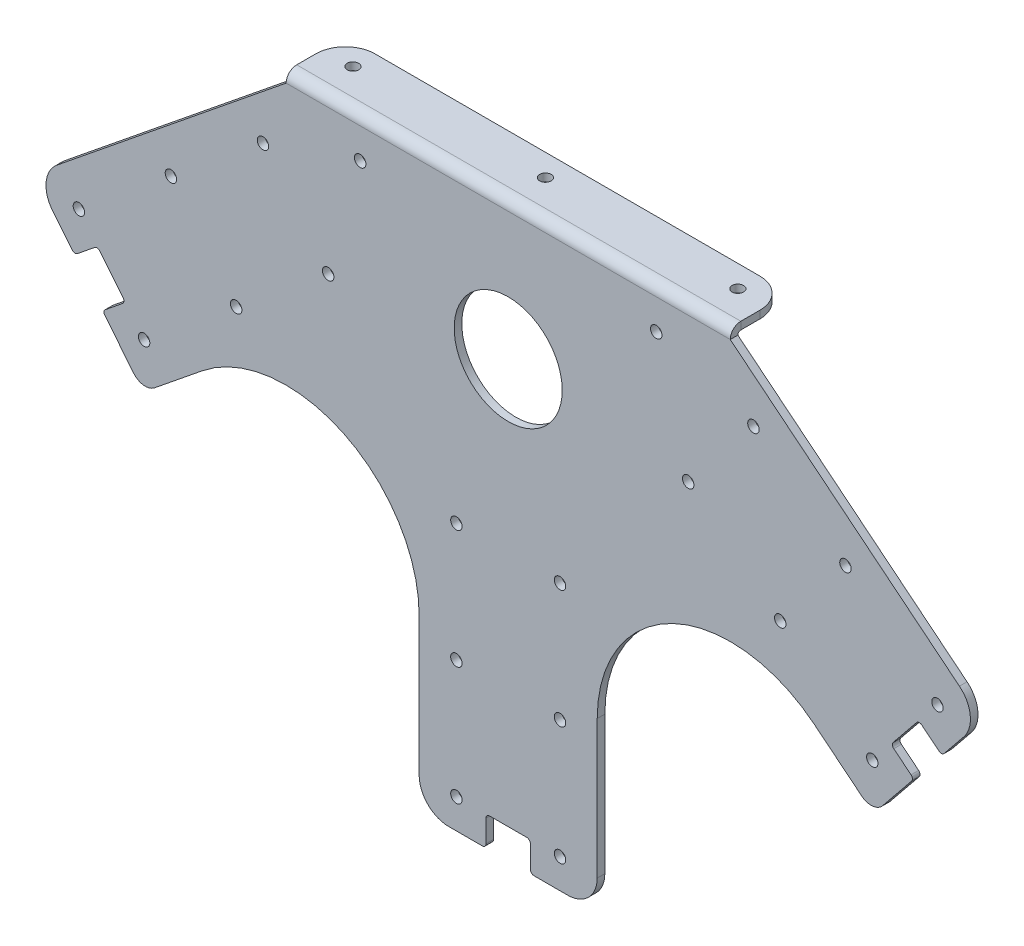
SolidWorks part; units mm, degrees
note: The reader was unsure of these and kept them because the rebuilt part matched: flange length of "Edge-Flange1".
material "5052-H32"
ref_plane "Front Plane" through (0, 0, 0) normal (0, 0, 1) x (1, 0, 0)
ref_plane "Top Plane" through (0, 0, 0) normal (0, 1, 0) x (1, 0, 0)
ref_plane "Right Plane" through (0, 0, 0) normal (1, 0, 0) x (0, 0, -1)
sketch "Sketch1" plane through (0, 0, 0) normal (0, 0, 1) x (1, 0, 0)
  line L0 (0, 0) -> (0, -50000) construction
  line L1 (95.25, 54.9275) -> (-95.25, 54.9275)
  line L2 (-95.25, 54.9275) -> (-203.4372, -32.6808) construction
  line L4 (-156.6259, -90.488) -> (0, 36.3452) construction
  line L5 (-38.1889, -186.3725) -> (-38.1889, 5.4205) construction
  line L8 (38.1889, -186.3725) -> (38.1889, 5.4205) construction
  line L9 (156.6259, -90.488) -> (0, 36.3452) construction
  line L10 (95.25, 54.9275) -> (203.4372, -32.6808) construction
  line L11 (-203.4372, -32.6808) -> (-156.6259, -90.488)
  line L12 (-156.6259, -90.488) -> (-38.1889, -186.3725)
  line L13 (156.6259, -90.488) -> (203.4372, -32.6808)
  line L14 (38.1889, -186.3725) -> (156.6259, -90.488)
  line L15 (-95.25, 54.9275) -> (-203.4372, -32.6808)
  line L16 (203.4372, -32.6808) -> (95.25, 54.9275)
  line L17 (38.1889, -186.3725) -> (-38.1889, -186.3725)
  circle A0 centre (0, 0) radius 23.1775
  point P7 (0, 23.1775)
  point P15 (0, -186.3725)
  point P20 (0, 54.9275)
  dimension "D1" = 46.355
  dimension "D2" = 39
  dimension "D3" = 95.25
  dimension "D4" = 31.75
  dimension "D5" = 241.3
  dimension "D6" = 74.3839
  dimension "D7" = 38.1889
  dimension "D8" = 152.4
base flange "Base-Flange1" sketch "Sketch1" thickness 3.2639 reverse thickness direction no parameters "D1"=1.27
edge flange "Edge-Flange1" sketch "Sketch8" flange angle 90 flange length 25.4 flange position bend outside bend radius 1.27 thickness 3.2639 relief rectangular parameters "D6"=10
sketch "Sketch8" plane through (0, 54.9275, -3.2639) normal (0, -1, 0) x (-1, 0, 0)
  line L2 (-95.25, 0) -> (-95.25, 22.1361)
  line L3 (-95.25, 22.1361) -> (95.25, 22.1361)
  line L4 (95.25, 22.1361) -> (95.25, 0)
  line L5 (95.25, 0) -> (-95.25, 0) construction
  line L6 (95.25, 0) -> (-95.25, 0)
bend "EdgeBend1" bend radius 1.27 bend angle 90 parameters "D5"=1
edge flange "Edge-Flange2" [suppressed] sketch "Sketch11" flange angle 90 flange position material inside bend radius 1.27 thickness 3.2639
sketch "Sketch11" plane through (0, 56.1975, -25.4) normal (0, 0, 1) x (-1, 0, 0)
  line L2 (-95.25, 0) -> (-95.25, 9.4361)
  line L3 (-95.25, 9.4361) -> (95.25, 9.4361)
  line L4 (95.25, 9.4361) -> (95.25, 0)
  line L5 (95.25, 0) -> (-95.25, 0) construction
  line L6 (95.25, 0) -> (-95.25, 0)
bend "EdgeBend2" bend radius 1.27 bend angle 90 parameters "D5"=2, "D6"=10, "D7"=12.7
sketch "Sketch12" [suppressed] plane through (0, 0, -25.4) normal (0, 0, -1) x (-1, 0, 0)
  line L4 (199.0941, -29.1638) -> (95.25, 54.9275)
  line L5 (95.25, 54.9275) -> (-95.25, 54.9275)
  line L6 (199.0941, -29.1638) -> (95.25, 54.9275)
  line L7 (-95.25, 54.9275) -> (-199.0941, -29.1638)
  line L12 (95.25, 46.7614) -> (95.25, 54.9275)
  line L13 (95.25, 54.9275) -> (-95.25, 54.9275)
  line L14 (-95.25, 54.9275) -> (-95.25, 46.7614)
  line L15 (-95.25, 46.7614) -> (95.25, 46.7614)
  line L16 (95.25, 46.7614) -> (95.25, 54.9275)
  line L18 (-95.25, 54.9275) -> (-95.25, 46.7614)
  line L19 (-95.25, 46.7614) -> (95.25, 46.7614)
  line L24 (-95.25, 54.9275) -> (-199.0941, -29.1638)
  line L25 (-199.0941, -29.1638) -> (-143.1475, -98.2521)
  line L26 (-199.0941, -29.1638) -> (-143.1475, -98.2521)
  line L27 (-143.1475, -98.2521) -> (-44.45, -186.3725)
  line L28 (-143.1475, -98.2521) -> (-44.45, -186.3725)
  line L29 (-44.45, -186.3725) -> (44.45, -186.3725)
  line L30 (-44.45, -186.3725) -> (44.45, -186.3725)
  line L31 (44.45, -186.3725) -> (143.1475, -98.2521)
  line L32 (44.45, -186.3725) -> (143.1475, -98.2521)
  line L33 (143.1475, -98.2521) -> (199.0941, -29.1638)
  line L34 (143.1475, -98.2521) -> (199.0941, -29.1638)
  circle A0 centre (0, 0) radius 23.1775 construction
  circle A1 centre (0, 0) radius 23.1775
  dimension "D1" = 0
  dimension "D2" = 0
extrude "Boss-Extrude1" [suppressed] add sketch "Sketch12" against normal up to surface (3.2639 mm away)
sketch "Sketch13" plane through (0, 0, 0) normal (0, 0, 1) x (1, 0, 0)
  line L0 (-156.6259, -90.488) -> (-38.1889, 5.4205)
  line L1 (-38.1889, 5.4205) -> (-38.1889, -186.3725)
  line L2 (38.1889, -186.3725) -> (38.1889, 5.4205)
  line L3 (38.1889, 5.4205) -> (156.6259, -90.488)
  line L6 (-38.1889, -186.3725) -> (-156.6259, -90.488)
  line L7 (38.1889, -186.3725) -> (156.6259, -90.488)
extrude "Cut-Extrude1" cut sketch "Sketch13" along normal through all and the other way through all normal cut yes
fillet "Fillet1" radius 57.15 2 edges at (38.1889, 5.4205, -1.6319) (-38.1889, 5.4205, -1.6319)
sketch "Sketch14" plane through (0, 0, 0) normal (0, 0, 1) x (1, 0, 0)
  line L0 (-154.0885, 7.281) -> (-107.2772, -50.5261) construction
  line L1 (-95.25, 54.9275) -> (-203.4372, -32.6808) construction
  line L2 (-156.6259, -90.488) -> (-131.3046, -69.9831) construction
  line L3 (-203.4372, -32.6808) -> (-156.6259, -90.488) construction
  line L4 (-144.6695, -4.3505) -> (-105.1905, 27.619) construction
  line L5 (-105.1905, 27.619) -> (-77.2172, -6.9251) construction
  line L6 (-77.2172, -6.9251) -> (-116.6962, -38.8946) construction
  line L7 (-184.1485, -36.3199) -> (-156.1752, -70.8641) construction
  line L8 (0, 0) -> (0, -186.3725) construction
  line L9 (-38.1889, -186.3725) -> (38.1889, -186.3725) construction
  point P4 (-116.6962, -38.8946)
  point P9 (-144.6695, -4.3505)
  point P10 (-105.1905, 27.619)
  point P11 (-77.2172, -6.9251)
  point P14 (-184.1485, -36.3199)
  point P17 (-156.1752, -70.8641)
  point P25 (77.2172, -6.9251)
  point P26 (116.6962, -38.8946)
  point P27 (156.1752, -70.8641)
  point P28 (184.1485, -36.3199)
  point P29 (144.6695, -4.3505)
  point P30 (105.1905, 27.619)
  dimension "D1" = 114.3
  dimension "D2" = 14.9669
  dimension "D3" = 44.45
  dimension "D4" = 50.8
  dimension "D5" = 50.8
hole_wizard "#10 (0.1935) Diameter Hole2" positions "Sketch15" profile "Sketch16" hole size "#10" standard "ANSI Inch" end condition through all
sketch "Sketch15" plane through (0, 0, 0) normal (0, 0, 1) x (1, 0, 0)
  point P0 (-144.6695, -4.3505)
  point P3 (-116.6962, -38.8946)
  point P6 (-77.2172, -6.9251)
  point P8 (-105.1905, 27.619)
  point P10 (-156.1752, -70.8641)
  point P12 (-184.1485, -36.3199)
  point P14 (105.1905, 27.619)
  point P17 (77.2172, -6.9251)
  point P20 (144.6695, -4.3505)
  point P23 (116.6962, -38.8946)
  point P26 (156.1752, -70.8641)
  point P29 (184.1485, -36.3199)
sketch "Sketch16" plane through (-144.6695, -4.3505, 0) normal (1, 0, 0) x (0, -1, 0)
  line L0 (0, 0) -> (0, 25.4)
  line L1 (0, 25.4) -> (2.4574, 25.4)
  line L2 (2.4574, 25.4) -> (2.4574, 0)
  line L5 (2.4574, 0) -> (0, 0)
  line L11 (0, -6.35) -> (0, 107.95) construction
  dimension "Thru Hole Dia." = 4.9149
  dimension "Thru Hole Depth" = 25.4
mirror "Mirror1" [suppressed] about plane through (0, 0, 0) normal (1, 0, 0)
sketch "Sketch17" plane through (0, 0, 0) normal (0, 0, 1) x (1, 0, 0)
  line L0 (-38.1889, -186.3725) -> (38.1889, -186.3725) construction
  line L1 (-22.225, -173.6725) -> (22.225, -173.6725)
  line L2 (-22.225, -173.6725) -> (-22.225, -122.8725)
  line L3 (-22.225, -122.8725) -> (22.225, -122.8725)
  line L4 (22.225, -173.6725) -> (22.225, -122.8725)
  point P6 (0, -186.3725)
  point P7 (0, -173.6725)
  point P8 (-22.225, -72.0725)
  point P9 (22.225, -72.0725)
  dimension "D1" = 44.45
  dimension "D2" = 50.8
  dimension "D3" = 12.7
  dimension "D4" = 50.8
hole_wizard "#10 (0.1935) Diameter Hole1" positions "Sketch18" profile "Sketch19" hole size "#10" standard "ANSI Inch" end condition through all
sketch "Sketch18" plane through (0, 0, 0) normal (0, 0, 1) x (1, 0, 0)
  point P0 (-22.225, -173.6725)
  point P3 (-22.225, -122.8725)
  point P6 (-22.225, -72.0725)
  point P9 (22.225, -72.0725)
  point P12 (22.225, -122.8725)
  point P15 (22.225, -173.6725)
sketch "Sketch19" plane through (-22.225, -173.6725, 0) normal (1, 0, 0) x (0, -1, 0)
  line L0 (0, 0) -> (0, 25.4)
  line L1 (0, 25.4) -> (2.4574, 25.4)
  line L2 (2.4574, 25.4) -> (2.4574, 0)
  line L5 (2.4574, 0) -> (0, 0)
  line L11 (0, -6.35) -> (0, 107.95) construction
  dimension "Thru Hole Dia." = 4.9149
  dimension "Thru Hole Depth" = 25.4
sketch "Sketch20" plane through (0, 0, 0) normal (0, 0, 1) x (1, 0, 0)
  line L0 (156.6259, -90.488) -> (203.4372, -32.6808) construction
  line L1 (-38.1889, -186.3725) -> (38.1889, -186.3725) construction
  line L2 (-203.4372, -32.6808) -> (-156.6259, -90.488) construction
  line L3 (156.6259, -90.488) -> (203.4372, -32.6808) construction
  line L4 (-38.1889, -186.3725) -> (38.1889, -186.3725) construction
  line L5 (-203.4372, -32.6808) -> (-156.6259, -90.488) construction
  line L6 (-186.0259, -54.1821) -> (-176.1561, -46.1897)
  line L7 (-176.1561, -46.1897) -> (-164.1676, -60.9943)
  line L8 (-164.1676, -60.9943) -> (-174.0373, -68.9867)
  line L9 (-9.525, -186.3725) -> (-9.525, -173.6725)
  line L10 (-9.525, -173.6725) -> (9.525, -173.6725)
  line L11 (9.525, -173.6725) -> (9.525, -186.3725)
  line L12 (174.0373, -68.9867) -> (164.1676, -60.9943)
  line L13 (164.1676, -60.9943) -> (176.1561, -46.1897)
  line L14 (176.1561, -46.1897) -> (186.0259, -54.1821)
  line L15 (-186.0259, -54.1821) -> (-174.0373, -68.9867)
  line L16 (-9.525, -186.3725) -> (9.525, -186.3725)
  line L17 (186.0259, -54.1821) -> (174.0373, -68.9867)
  point P19 (-180.0316, -61.5844)
  point P20 (-180.0316, -61.5844)
  point P21 (0, -186.3725)
  point P22 (0, -186.3725)
  point P23 (180.0316, -61.5844)
  point P24 (180.0316, -61.5844)
  dimension "D1" = 19.05
  dimension "D2" = 12.7
extrude "Cut-Extrude2" cut sketch "Sketch20" against normal through all normal cut yes
sketch "Sketch21" plane through (0, 59.4614, 0) normal (0, 1, 0) x (1, 0, 0)
  line L1 (-95.25, 3.2639) -> (-203.4372, 3.2639) construction
  line L2 (-82.55, 15.9639) -> (0, 15.9639) construction
  line L3 (0, 15.9639) -> (82.55, 15.9639) construction
  line L4 (-95.25, 4.5339) -> (-95.25, 25.4) construction
  point P0 (-82.55, 15.9639)
  point P1 (0, 15.9639)
  point P2 (82.55, 15.9639)
  dimension "D1" = 12.7
  dimension "D2" = 12.7
hole_wizard "#10 (0.1935) Diameter Hole3" positions "Sketch22" profile "Sketch23" hole size "#10" standard "ANSI Inch" end condition up to next
sketch "Sketch22" plane through (0, 59.4614, 0) normal (0, 1, 0) x (1, 0, 0)
  point P0 (-82.55, 15.9639)
  point P3 (0, 15.9639)
  point P6 (82.55, 15.9639)
sketch "Sketch23" plane through (-82.55, 59.4614, -15.9639) normal (1, 0, 0) x (0, 0, 1)
  line L0 (0, 0) -> (0, 3.2639)
  line L1 (0, 3.2639) -> (2.4574, 3.2639)
  line L2 (2.4574, 3.2639) -> (2.4574, 0)
  line L5 (2.4574, 0) -> (0, 0)
  line L11 (0, -6.35) -> (0, 107.95) construction
  dimension "Thru Hole Dia." = 4.9149
  dimension "Thru Hole Depth" = 3.2639
sketch "Sketch25" plane through (0, 0, 0) normal (0, 0, 1) x (1, 0, 0)
  line L1 (-95.25, 56.1975) -> (95.25, 56.1975) construction
  line L3 (-63.5, 41.91) -> (63.5, 41.91) construction
  point P0 (-63.5, 41.91)
  point P1 (63.5, 41.91)
  point P6 (0, 41.91)
  point P7 (-63.5, -34.29)
  point P8 (63.5, -34.29)
  dimension "D1" = 14.2875
  dimension "D2" = 127
  dimension "D3" = 76.2
hole_wizard "#10 (0.1935) Diameter Hole4" positions "Sketch26" profile "Sketch27" hole size "#10" standard "ANSI Inch" end condition up to next
sketch "Sketch26" plane through (0, 0, 0) normal (0, 0, 1) x (1, 0, 0)
  point P0 (-63.5, 41.91)
  point P3 (63.5, 41.91)
sketch "Sketch27" plane through (-63.5, 41.91, 0) normal (1, 0, 0) x (0, -1, 0)
  line L0 (0, 0) -> (0, 3.2639)
  line L1 (0, 3.2639) -> (2.4574, 3.2639)
  line L2 (2.4574, 3.2639) -> (2.4574, 0)
  line L5 (2.4574, 0) -> (0, 0)
  line L11 (0, -6.35) -> (0, 107.95) construction
  dimension "Thru Hole Dia." = 4.9149
  dimension "Thru Hole Depth" = 3.2639
fillet "Fillet2" radius 12.7 6 edges at (203.4372, -32.6808, -1.632) (38.1889, -186.3725, -1.6319) (-38.1889, -186.3725, -1.6319) (-203.4372, -32.6808, -1.632) (95.25, 57.8295, -25.4) (-95.25, 57.8295, -25.4)
fillet "Fillet3" radius 1.5875 12 edges at (164.1676, -60.9943, -1.632) (174.0373, -68.9867, -1.632) (186.0259, -54.1821, -1.632) (176.1561, -46.1897, -1.632) (9.525, -173.6725, -1.632) (9.525, -186.3725, -1.632) (-9.525, -186.3725, -1.632) (-9.525, -173.6725, -1.632) (-176.1561, -46.1897, -1.632) (-174.0373, -68.9867, -1.632) (-164.1676, -60.9943, -1.632) (-186.0259, -54.1821, -1.632)
fillet "Fillet4" radius 6.35 2 edges at (156.6259, -90.488, -1.6319) (-156.6259, -90.488, -1.6319)
sketch "Bend-Lines1" [suppressed] plane through (0, 0, 0) normal (0, 1, 0) x (1, 0, 0)
sketch "Bounding-Box1" [suppressed] plane through (0, 0, 0) normal (0, 1, 0) x (1, 0, 0)
sheet metal parameters "Sheet-Metal1" thickness 3.2639 parameters "D1"=1.27
flat pattern "Flat-Pattern1" [suppressed]
sketch "Bend-Lines2" plane through (0, 0, 0) normal (0, 1, 0) x (1, 0, 0)
sketch3d "Bounding-Box2" [suppressed]
  line L0 (-16.1575, -240.4848, 0) -> (208.6016, -39.8125, 0) construction
  line L1 (-202.2868, -32.0143, 0) -> (22.4723, 168.658, 0) construction
  line L2 (-16.1575, -240.4848, 0) -> (-202.2868, -32.0143, 0) construction
  line L3 (208.6016, -39.8125, 0) -> (22.4723, 168.658, 0) construction
sheet metal parameters "Sheet-Metal2" thickness 3.2639 parameters "D1"=1.27
flat pattern "Flat-Pattern1"
sketch "Bend-Lines2" plane through (0, 0, 0) normal (0, 0, 1) x (1, 0, 0)
  line L0 (95.25, 57.2067) -> (-95.25, 57.2067) construction
  line L1 (95.25, 57.2067) -> (-95.25, 57.2067) construction
sketch3d "Bounding-Box2" [suppressed]
  line L0 (-7.6051, -241.1975, 0) -> (207.1023, -37.6094, 0) construction
  line L1 (-209.647, -28.1206, 0) -> (5.0604, 175.4675, 0) construction
  line L2 (-7.6051, -241.1975, 0) -> (-209.647, -28.1206, 0) construction
  line L3 (207.1023, -37.6094, 0) -> (5.0604, 175.4675, 0) construction
bend of the flat pattern "Flatten-<EdgeBend1>1"
sheet metal parameters "Sheet-Metal3" thickness 3.2639 parameters "D1"=1.27
flat pattern "Flat-Pattern1"
sketch "Bend-Lines2" plane through (0, 0, 0) normal (0, 0, 1) x (1, 0, 0)
  line L0 (95.25, 57.2067) -> (-95.25, 57.2067) construction
  line L1 (95.25, 57.2067) -> (-95.25, 57.2067) construction
  line L2 (95.25, 78.0973) -> (-95.25, 78.0973) construction
  line L3 (95.25, 78.0973) -> (-95.25, 78.0973) construction
sketch3d "Bounding-Box2" [suppressed]
  line L0 (-10.7511, 183.1838, 0) -> (214.7024, -18.1085, 0) construction
  line L1 (-209.2961, -39.1925, 0) -> (16.1575, -240.4848, 0) construction
  line L2 (-10.7511, 183.1838, 0) -> (-209.2961, -39.1925, 0) construction
  line L3 (214.7024, -18.1085, 0) -> (16.1575, -240.4848, 0) construction
bend of the flat pattern "Flatten-<EdgeBend2>1"
bend of the flat pattern "Flatten-<EdgeBend1>1"
sheet metal parameters "Sheet-Metal4" thickness 3.2639 parameters "D1"=1.27
flat pattern "Flat-Pattern1" [suppressed]
sketch "Bend-Lines2" plane through (0, 0, 0) normal (0, 0, 1) x (1, 0, 0)
  line L0 (76.2, 62.6042) -> (-76.2, 62.6042) construction
  line L1 (76.2, 62.6042) -> (-76.2, 62.6042) construction
  line L2 (76.2, 134.2948) -> (-76.2, 134.2948) construction
  line L3 (76.2, 134.2948) -> (-76.2, 134.2948) construction
sketch3d "Bounding-Box2" [suppressed]
  line L0 (-384.265, -189.1411, 0) -> (384.265, -189.1411, 0) construction
  line L1 (-384.265, 386.04, 0) -> (384.265, 386.04, 0) construction
  line L2 (-384.265, -189.1411, 0) -> (-384.265, 386.04, 0) construction
  line L3 (384.265, -189.1411, 0) -> (384.265, 386.04, 0) construction
bend of the flat pattern "Flatten-<EdgeBend2>1"
bend of the flat pattern "Flatten-<EdgeBend1>1"
sheet metal parameters "Sheet-Metal5" thickness 3.2639 parameters "D1"=1.27
flat pattern "Flat-Pattern1"
sketch "Bend-Lines2" plane through (0, 0, 0) normal (0, 0, 1) x (1, 0, 0)
  line L0 (95.25, 57.2067) -> (-95.25, 57.2067) construction
  line L1 (95.25, 57.2067) -> (-95.25, 57.2067) construction
sketch3d "Bounding-Box2" [suppressed]
  line L0 (-7.6051, -241.1975, 0) -> (207.1023, -37.6094, 0) construction
  line L1 (-209.647, -28.1206, 0) -> (5.0604, 175.4675, 0) construction
  line L2 (-7.6051, -241.1975, 0) -> (-209.647, -28.1206, 0) construction
  line L3 (207.1023, -37.6094, 0) -> (5.0604, 175.4675, 0) construction
bend of the flat pattern "Flatten-<EdgeBend1>1"
sheet metal parameters "Sheet-Metal6" thickness 3.2639 parameters "D1"=1.27
flat pattern "Flat-Pattern1" [suppressed]
sketch "Bend-Lines2" plane through (0, 0, 0) normal (0, 0, 1) x (1, 0, 0)
  line L0 (76.2, 81.6542) -> (-76.2, 81.6542) construction
  line L1 (76.2, 81.6542) -> (-76.2, 81.6542) construction
  line L2 (76.2, 153.3448) -> (-76.2, 153.3448) construction
  line L3 (76.2, 153.3448) -> (-76.2, 153.3448) construction
sketch3d "Bounding-Box2" [suppressed]
  line L0 (192.7441, 396.9239, 0) -> (192.7441, -161.925, 0) construction
  line L1 (-192.7441, 396.9239, 0) -> (-192.7441, -161.925, 0) construction
  line L2 (192.7441, 396.9239, 0) -> (-192.7441, 396.9239, 0) construction
  line L3 (192.7441, -161.925, 0) -> (-192.7441, -161.925, 0) construction
bend of the flat pattern "Flatten-<EdgeBend1>1"
sheet metal parameters "Sheet-Metal7" thickness 3.2639 parameters "D1"=1.27
flat pattern "Flat-Pattern1"
sketch "Bend-Lines2" plane through (0, 0, 0) normal (0, 0, 1) x (1, 0, 0)
  line L0 (95.25, 57.2067) -> (-95.25, 57.2067) construction
  line L1 (95.25, 57.2067) -> (-95.25, 57.2067) construction
  point P2 (95.25, 153.5226)
  point P3 (-95.25, 153.5226)
sketch3d "Bounding-Box2" [suppressed]
  line L0 (-7.6051, -241.1975, 0) -> (207.1023, -37.6094, 0) construction
  line L1 (-209.647, -28.1206, 0) -> (5.0604, 175.4675, 0) construction
  line L2 (-7.6051, -241.1975, 0) -> (-209.647, -28.1206, 0) construction
  line L3 (207.1023, -37.6094, 0) -> (5.0604, 175.4675, 0) construction
bend of the flat pattern "Flatten-<EdgeBend1>1"
sheet metal parameters "Sheet-Metal8" thickness 3.2639 parameters "D1"=1.27
flat pattern "Flat-Pattern1"
sketch "Bend-Lines2" plane through (0, 0, 0) normal (0, 0, 1) x (1, 0, 0)
  line L0 (95.25, 57.2067) -> (-95.25, 57.2067) construction
  line L1 (95.25, 57.2067) -> (-95.25, 57.2067) construction
  point P2 (95.25, 160.6663)
  point P3 (-95.25, 160.6663)
sketch3d "Bounding-Box2" [suppressed]
  line L0 (-7.6051, -241.1975, 0) -> (207.1023, -37.6094, 0) construction
  line L1 (-209.647, -28.1206, 0) -> (5.0604, 175.4675, 0) construction
  line L2 (-7.6051, -241.1975, 0) -> (-209.647, -28.1206, 0) construction
  line L3 (207.1023, -37.6094, 0) -> (5.0604, 175.4675, 0) construction
bend of the flat pattern "Flatten-<EdgeBend1>1"
sheet metal parameters "Sheet-Metal9" thickness 3.2639 parameters "D1"=1.27
flat pattern "Flat-Pattern1"
sketch "Bend-Lines2" plane through (0, 0, 0) normal (0, 0, 1) x (1, 0, 0)
  line L0 (95.25, 57.2067) -> (-95.25, 57.2067) construction
  line L1 (95.25, 57.2067) -> (-95.25, 57.2067) construction
sketch3d "Bounding-Box2" [suppressed]
  line L0 (-7.6051, -241.1975, 0) -> (207.1023, -37.6094, 0) construction
  line L1 (-209.647, -28.1206, 0) -> (5.0604, 175.4675, 0) construction
  line L2 (-7.6051, -241.1975, 0) -> (-209.647, -28.1206, 0) construction
  line L3 (207.1023, -37.6094, 0) -> (5.0604, 175.4675, 0) construction
bend of the flat pattern "Flatten-<EdgeBend1>1"
sheet metal parameters "Sheet-Metal17" thickness 3.2639 parameters "D1"=1.27
flat pattern "Flat-Pattern1" [suppressed]
sketch "Bend-Lines2" plane through (0, 0, 0) normal (0, 0, 1) x (1, 0, 0)
  line L0 (95.25, 57.2067) -> (-95.25, 57.2067) construction
  line L1 (95.25, 57.2067) -> (-95.25, 57.2067) construction
sketch3d "Bounding-Box2" [suppressed]
  line L0 (-7.6051, -241.1975, 0) -> (207.1023, -37.6094, 0) construction
  line L1 (-209.647, -28.1206, 0) -> (5.0604, 175.4675, 0) construction
  line L2 (-7.6051, -241.1975, 0) -> (-209.647, -28.1206, 0) construction
  line L3 (207.1023, -37.6094, 0) -> (5.0604, 175.4675, 0) construction
bend of the flat pattern "Flatten-<EdgeBend1>1"
sketch "Sketch21-1" [suppressed] plane through (0, 54.952, 0) normal (0, 0, 1) x (1, 0, 0)
  line L1 (-95.25, -0.0245) -> (-199.0941, -84.1158) construction
  line L2 (-82.55, 15.9639) -> (0, 15.9639) construction
  line L3 (0, 15.9639) -> (82.55, 15.9639) construction
  line L4 (-95.25, -0.0245) -> (-95.25, 25.4) construction
  point P0 (-82.55, 15.9639)
  point P1 (0, 15.9639)
  point P2 (82.55, 15.9639)
  dimension "D1" = 4.4329
  dimension "D2" = 12.7
sheet metal parameters "Sheet-Metal18" thickness 3.2639 parameters "D1"=1.27
flat pattern "Flat-Pattern1" [suppressed]
sketch "Bend-Lines2" plane through (0, 0, 0) normal (0, 0, 1) x (1, 0, 0)
  line L0 (95.25, 57.2067) -> (-95.25, 57.2067) construction
  line L1 (95.25, 57.2067) -> (-95.25, 57.2067) construction
sketch3d "Bounding-Box2" [suppressed]
  line L0 (-1.272, -246.2193, 0) -> (207.7365, -38.8641, 0) construction
  line L1 (-207.4635, -38.3838, 0) -> (1.5451, 168.9714, 0) construction
  line L2 (-1.272, -246.2193, 0) -> (-207.4635, -38.3838, 0) construction
  line L3 (207.7365, -38.8641, 0) -> (1.5451, 168.9714, 0) construction
bend of the flat pattern "Flatten-<EdgeBend1>1"
sketch "Sketch21-1" [suppressed] plane through (0, 54.952, 0) normal (0, 0, 1) x (1, 0, 0)
  line L1 (-95.25, -0.0245) -> (-193.5675, -79.6404) construction
  line L2 (-82.55, 15.9639) -> (0, 15.9639) construction
  line L3 (0, 15.9639) -> (82.55, 15.9639) construction
  line L4 (-95.25, -0.0245) -> (-95.25, 12.7) construction
  point P0 (-82.55, 15.9639)
  point P1 (0, 15.9639)
  point P2 (82.55, 15.9639)
  dimension "D1" = 4.4329
  dimension "D2" = 12.7
